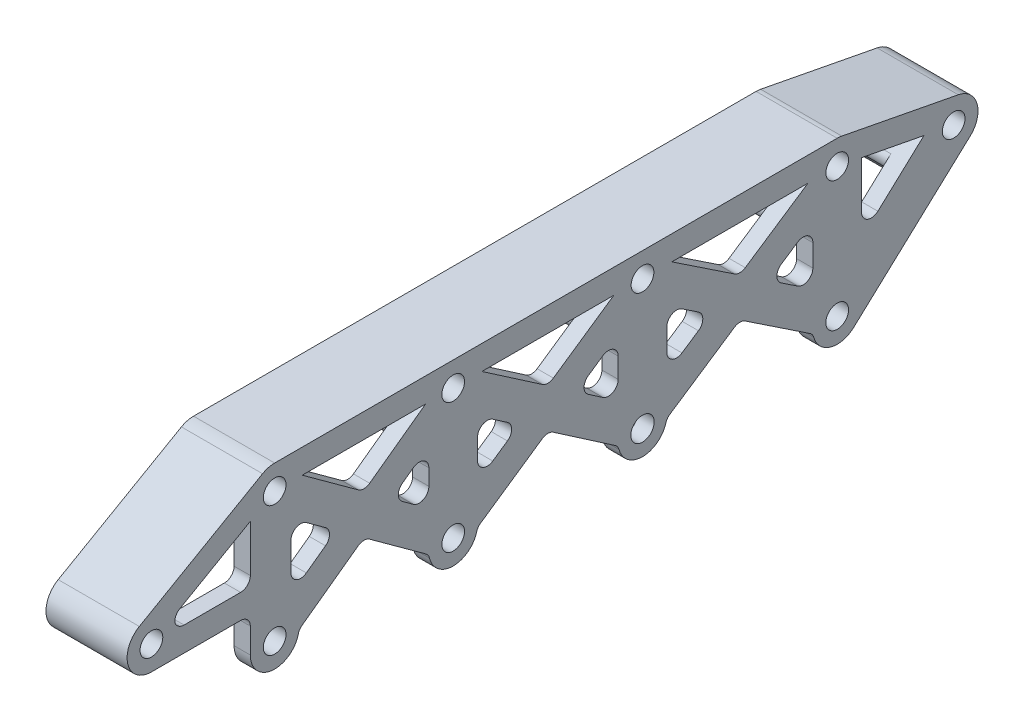
SolidWorks part; units mm, degrees
ref_plane "Front Plane" through (0, 0, 0) normal (0, 0, 1) x (1, 0, 0)
ref_plane "Top Plane" through (0, 0, 0) normal (0, 1, 0) x (1, 0, 0)
ref_plane "Right Plane" through (0, 0, 0) normal (1, 0, 0) x (0, 0, -1)
sketch "Sketch1" plane through (0, 0, 0) normal (1, 0, 0) x (0, 0, -1)
  line L0 (0, 0) -> (0, 25.4)
  line L1 (0, 25.4) -> (38.1, 25.4)
  line L2 (38.1, 25.4) -> (38.1, 0)
  line L3 (0, 25.4) -> (-37.0443, 25.4)
  line L4 (-37.0443, 25.4) -> (-71.9773, 25.4)
  line L5 (-71.9773, 25.4) -> (-71.9773, 0)
  line L6 (-37.0443, 25.4) -> (-37.0443, 0)
  line L7 (38.1, 25.4) -> (60.8901, 25.4)
  line L8 (60.8901, 25.4) -> (60.8901, 21.0111)
  line L9 (-71.9773, 25.4) -> (-71.9773, 11.5732)
  line L10 (-71.9773, 11.5732) -> (-96.0904, 11.5732)
  line L11 (-96.0904, 11.5732) -> (-71.9773, 25.4)
  line L12 (60.8901, 21.0111) -> (38.1, 25.4)
  line L13 (38.1, 0) -> (60.8901, 21.0111)
  line L14 (-67.2148, 33.6208) -> (-67.2148, 6.8107)
  line L15 (-67.2148, 6.8107) -> (-113.97, 6.8107)
  line L16 (-113.97, 6.8107) -> (-67.2148, 33.6208)
  line L17 (61.7907, 25.6877) -> (39.0006, 30.0766)
  line L18 (33.3375, 25.4) -> (33.3375, -10.8684)
  line L19 (33.3375, -10.8684) -> (64.1182, 17.5096)
  line L20 (0, 30.1625) -> (-37.0443, 30.1625)
  line L21 (0, 20.6375) -> (38.1, 20.6375)
  line L22 (-37.0443, 30.1625) -> (-71.9773, 30.1625)
  line L23 (-76.7398, 25.4) -> (-76.7398, 0)
  line L24 (-41.8068, 25.4) -> (-41.8068, 0)
  line L25 (4.7625, 0) -> (4.7625, 25.4)
  line L26 (-76.7398, 17.1792) -> (-76.7398, 16.3357)
  line L27 (-76.7398, 16.3357) -> (-78.2108, 16.3357)
  line L28 (-78.2108, 16.3357) -> (-76.7398, 17.1792)
  line L29 (59.9895, 16.3346) -> (37.1994, 20.7234)
  line L30 (42.8625, 25.4) -> (42.8625, 10.8684)
  line L31 (42.8625, 10.8684) -> (57.6619, 24.5126)
  line L32 (0, 20.6375) -> (-37.0443, 20.6375)
  line L33 (0, 30.1625) -> (38.1, 30.1625)
  line L34 (-37.0443, 20.6375) -> (-71.9773, 20.6375)
  line L35 (-67.2148, 25.4) -> (-67.2148, 0)
  line L36 (-32.2818, 25.4) -> (-32.2818, 0)
  line L37 (-4.7625, 0) -> (-4.7625, 25.4)
  line L38 (-71.9773, 0) -> (-37.0443, 25.4)
  line L39 (-37.0443, 0) -> (-71.9773, 25.4)
  line L40 (-37.0443, 0) -> (0, 25.4)
  line L41 (0, 0) -> (-37.0443, 25.4)
  line L42 (0, 0) -> (38.1, 25.4)
  line L43 (38.1, 0) -> (0, 25.4)
  line L44 (39.8612, 2.6418) -> (1.7612, 28.0418)
  line L45 (1.7612, -2.6418) -> (39.8612, 22.7582)
  line L46 (1.7955, 2.6186) -> (-35.2489, 28.0186)
  line L47 (-35.2489, -2.6186) -> (1.7955, 22.7814)
  line L48 (-75.1523, 25.4) -> (-75.1523, -6.2341)
  line L49 (-75.1523, -6.2341) -> (-35.1772, 22.8321)
  line L50 (-35.1772, 2.5679) -> (-70.1102, 27.9679)
  line L51 (36.3388, -2.6418) -> (-1.7612, 22.7582)
  line L52 (-1.7612, 2.6418) -> (36.3388, 28.0418)
  line L53 (-1.7955, -2.6186) -> (-38.8398, 22.7814)
  line L54 (-38.8398, 2.6186) -> (-1.7955, 28.0186)
  line L55 (-68.8023, 25.4) -> (-68.8023, 6.2341)
  line L56 (-68.8023, 6.2341) -> (-38.9115, 27.9679)
  line L57 (-38.9115, -2.5679) -> (-73.8445, 22.8321)
  circle A0 centre (0, 0) radius 2.286
  circle A1 centre (38.1, 0) radius 2.2225
  circle A2 centre (-71.9773, 0) radius 2.2225
  circle A3 centre (-37.0443, 0) radius 2.2225
  circle A4 centre (-71.9773, 25.4) radius 2.2225
  circle A5 centre (-37.0443, 25.4) radius 2.2225
  circle A6 centre (0, 25.4) radius 2.2225
  circle A7 centre (38.1, 25.4) radius 2.2225
  circle A8 centre (60.8901, 21.0111) radius 2.2225
  circle A9 centre (-96.0904, 11.5732) radius 2.2225
  circle A10 centre (-71.9773, 0) radius 4.7625
  circle A11 centre (-37.0443, 0) radius 4.7625
  circle A12 centre (0, 0) radius 4.7625
  circle A13 centre (38.1, 0) radius 4.7625
  circle A14 centre (38.1, 25.4) radius 4.7625
  circle A15 centre (0, 25.4) radius 4.7625
  circle A16 centre (-37.0443, 25.4) radius 4.7625
  circle A17 centre (-71.9773, 25.4) radius 4.7625
  circle A18 centre (-96.0904, 11.5732) radius 4.7625
  circle A19 centre (60.8901, 21.0111) radius 4.7625
  dimension "D2" = 4.572
  dimension "D7" = 4.445
  dimension "D8" = 4.445
  dimension "D9" = 4.445
  dimension "D10" = 4.445
  dimension "D11" = 4.445
  dimension "D12" = 4.445
  dimension "D13" = 4.445
  dimension "D16" = 4.445
  dimension "D19" = 4.445
  dimension "D20" = 9.525
  dimension "D21" = 9.525
  dimension "D22" = 9.525
  dimension "D23" = 9.525
  dimension "D24" = 9.525
  dimension "D25" = 9.525
  dimension "D26" = 9.525
  dimension "D27" = 9.525
  dimension "D28" = 9.525
  dimension "D29" = 9.525
  dimension "D1" = 25.4
  dimension "D3" = 38.1
  dimension "D4" = 25.4
  dimension "D5" = 25.4
  dimension "D6" = 25.4
  dimension "D14" = 22.7901
  dimension "D15" = 4.3889
  dimension "D17" = 13.8268
  dimension "D18" = 24.113
  dimension "D30" = 4.7625
  dimension "D31" = 4.7625
  dimension "D32" = 3.175
  dimension "D33" = 3.175
extrude "Boss-Extrude1" add sketch "Sketch1" along normal blind 15.875 contours L5 A10 L48 L49 L38 A2 | L11 A18 L10 A9 | A18 L11 L23 A17 L16 | L4 A17 L11 A4 | A16 L22 L14 L50 L4 L56 | A18 L15 L23 L10 | L10 A18 L11 A9 | A17 L11 L23 L10 L48 | A17 L48 L10 L9 | L48 A17 L9 A4 L11 | L11 A17 L48 | A17 L23 L11 | L57 A17 L55 L39 A4 L9 | A4 L39 L55 L4 | A17 L50 L14 L22 | L4 L50 L14 | L39 A17 L4 L55 | L38 L57 L56 L35 | A10 L49 L57 L38 L35 | A10 L38 L35 L15 L56 L55 L5 | L38 A10 L5 A2 | L49 A10 | A10 L35 L38 | L48 A10 | A10 L48 L15 L23 | L48 L10 L23 L15 | L10 L48 L15 L5 | A10 L5 L15 L48 | L55 L57 L34 L9 L5 L15 | L55 A17 L39 | L9 A17 L57 | A17 L57 L34 L55 | A17 L34 L57 | L57 L55 L34 | L56 L15 L35 | A17 L14 L50 | L39 L56 L50 L34 | L57 L56 L39 L34 L14 | L34 L50 L4 L14 L39 | A17 L39 L14 | L34 L39 L35 | A17 L55 L34 L35 L39 | L57 L14 L34 L55 | L57 L38 L39 L56 | L56 L39 L38 L50 | L49 L50 L38 L39 | L57 L49 L39 L38 | L56 L50 L38 L34 | L50 L49 L24 L34 L38 | L24 L50 L49 L39 | A16 L46 L3 L54 A15 L20 | L3 A16 L4 A5 | L32 L46 L3 L36 L41 | A11 L6 L34 L49 L24 L50 | A11 L54 L36 L53 L32 L6 | A11 L24 L39 L49 L57 | A11 L50 L24 L39 | L50 A11 L39 A3 L6 | A11 L40 A3 L39 | A11 L39 L24 | L40 A11 L54 L6 A3 | A11 L40 L36 L54 | L54 L36 L40 L53 | A11 L47 L53 L40 L36 | L41 L54 L46 L32 | L53 L54 L41 L32 L36 | L56 L34 L38 L24 L4 | L4 A16 L38 A5 | A16 L56 L4 | A16 L24 L38 | A16 L38 L24 L34 L49 | L38 L34 L24 | L24 L49 L34 | L38 A16 L49 L6 A5 | A16 L3 L46 | L41 A16 L3 A5 | A16 L53 L32 L36 L41 | L32 L41 L36 | L53 L36 L32 | L53 A16 L41 A5 L6 | A16 L41 L36 | L6 A16 L53 L49 | L49 A16 L6 | A16 L49 L34 | A16 L32 L53 | L49 L53 L6 | L54 A11 L6 L50 | L6 A11 L50 | A11 L36 L40 | L6 L54 L50 | L54 L53 L40 L41 | L54 L41 L40 L46 | L53 L47 L41 L40 | L41 L47 L46 L40 | L46 L47 L37 L32 L40 | L54 L46 L40 L32 | L47 L41 L37 L46 | A12 L37 L41 L47 L53 | L54 L32 L40 L37 L3 | L40 L32 L37 | L1 A15 L3 A6 | A15 L54 L3 | L3 A15 L40 A6 | A15 L37 L40 | A15 L40 L37 L32 L47 | L37 L47 L32 | L40 A15 L47 L0 A6 | L47 A15 L0 | A15 L47 L32 | L51 A15 L43 A6 L0 | L0 A15 L51 L47 | A15 L21 L51 | A15 L51 L21 L25 L43 | L51 L25 L21 | A15 L44 L1 L52 A14 L33 | L43 A15 L1 A6 | A15 L1 L44 | A15 L43 L25 | L21 L44 L1 L25 L43 | L21 L43 L25 | L47 L51 L0 | A12 L46 L37 L41 | L46 A12 L41 A0 L0 | A12 L42 A0 L41 | A12 L41 L37 | L42 A12 L52 L0 A0 | L0 A12 L46 | L52 A12 L0 L46 | A12 L42 L25 L52 | A12 L25 L42 | L52 L25 L42 L51 | A12 L45 L51 L42 L25 | A12 L0 L32 L47 L37 L46 | A12 L52 L25 L51 L21 L0 | L51 L52 L43 L21 L25 | L43 L52 L44 L21 | L52 L43 L42 L44 | L52 L51 L42 L43 | L51 L45 L43 L42 | L43 L45 L44 L42 | L0 L52 L46 | L52 L21 L42 L18 L1 | L7 A14 L1 A7 | A19 L17 A14 L7 | A14 L52 L1 | L1 A14 L42 A7 | L52 L44 L42 L21 | L44 L45 L18 L21 L42 | L7 A19 L12 A8 L8 | A19 L7 L8 A8 L13 | A19 L29 L13 A13 L19 | L43 A13 L13 A1 | L51 L18 L43 L45 | L45 L43 L18 L44 | A13 L2 L29 L21 L45 L18 L44 | A13 L13 L29 L31 L30 L2 | A19 L12 L31 L29 L13 | A19 L13 L29 | L12 A19 L13 A8 | A19 L31 L12 | L2 A14 L12 A7 | A14 L2 L29 L30 L12 | L42 A14 L45 L2 A7 | L42 L21 L18 | A14 L18 L42 | A14 L42 L18 L21 L45 | L18 L45 L21 | L45 A14 L2 | A14 L45 L21 L29 | L29 L2 L21 | A14 L29 L21 | L12 A14 L7 A7 | A14 L12 L30 | A13 L18 L51 | A13 L43 L18 | A13 L44 L18 L43 | L44 A13 L43 A1 L2 | L2 A13 L44 | L13 A13 L2 A1 | A19 L7 L30 L12 L31 region at (0, 3.0311, 1.7302) region at (0, 3.0092, -1.756) region at (0, -2.2991, 0.7125) region at (0, 3.8327, -0.0083) region at (0, 2.2442, 4.5084) region at (0, 4.8141, 3.582) region at (0, 4.7476, -3.6056) region at (0, 2.1905, -4.5191) region at (0, 4.4269, 0.3865) region at (0, 4.4125, -0.4081) region at (0, 8.3932, 9.5713) region at (0, 5.5211, 10.9661) region at (0, 12.6923, 2.2321) region at (0, 5.4983, -11.216) region at (0, 8.3462, -9.794) region at (0, 12.691, -2.2413) region at (0, 10.7752, 18.5222) region at (0, 12.7, 15.7149) region at (0, 12.7, -16.1881) region at (0, 10.7921, -19.05) region at (0, 20.9731, 0.3865) region at (0, 20.684, -0.9787) region at (0, 20.6793, 0.9231) region at (0, 20.9875, -0.4081) region at (0, 16.8146, 9.7612) region at (0, 19.8533, 3.6188) region at (0, 14.6248, 18.5222) region at (0, 12.7, 21.3294) region at (0, 5.5211, 26.0782) region at (0, 19.8947, -3.6483) region at (0, 16.8393, -10.0149) region at (0, 14.6079, -19.05) region at (0, 12.7, -21.9119) region at (0, 5.4995, -26.8827) region at (0, 22.3881, 1.7178) region at (0, 21.5673, -0.0083) region at (0, 21.3763, -3.5648) region at (0, 21.3553, 3.5433) region at (0, 22.4099, -1.7433) region at (0, 21.1365, 5.4903) region at (0, 18.0818, 13.3021) region at (0, 8.3932, 27.473) region at (0, 16.8146, 27.2832) region at (0, 18.0818, 23.7423) region at (0, -4.6404, 37.1085) region at (0, 21.1667, -5.5562) region at (0, 18.0698, -13.6779) region at (0, 18.0698, -24.4221) region at (0, 16.8393, -28.0851) region at (0, 8.3462, -28.306) region at (0, -0.4926, -33.3517) region at (0, 24.3368, 3.4308) region at (0, 23.1558, 4.5084) region at (0, 23.2095, -4.5191) region at (0, 24.3585, -3.4399) region at (0, 22.4886, 7.5534) region at (0, 4.8141, 33.4624) region at (0, 2.2442, 32.5359) region at (0, 22.4886, 29.4909) region at (0, 21.1365, 31.5541)
sketch "Sketch2" plane through (0, 0, 0) normal (-1, 0, 0) x (0, 0, 1)
  line L12 (-38.1, 0) -> (-38.1, 19.05)
  line L13 (-38.1, 19.05) -> (71.9773, 19.924)
  line L14 (71.9773, 19.924) -> (71.9773, 0)
  line L15 (71.9773, 0) -> (-38.1, 0)
  line L16 (71.9773, 4.7625) -> (-38.1, 4.7625)
  line L17 (71.9773, -4.7625) -> (-38.1, -4.7625)
  line L18 (91.3067, 11.5732) -> (76.7398, 11.5732)
  line L19 (76.7398, 11.5732) -> (76.7398, 6.8107)
  line L20 (96.0904, 6.8107) -> (76.7398, 6.8107)
  line L24 (76.7398, 0) -> (76.7398, 6.8107)
  line L25 (76.7398, 6.8107) -> (96.0904, 6.8107)
  line L26 (98.4594, 15.7047) -> (74.3464, 29.5315)
  line L27 (71.9773, 30.1625) -> (-38.1, 30.1625)
  line L28 (-39.0006, 30.0766) -> (-61.7907, 25.6877)
  line L29 (-64.1182, 17.5096) -> (-41.3282, -3.5015)
  line L30 (-33.3852, -0.6727) -> (-19.05, 8.8841)
  line L31 (-19.05, 8.8841) -> (-4.7148, -0.6727)
  line L32 (4.7231, -0.6112) -> (18.5222, 8.8503)
  line L33 (18.5222, 8.8503) -> (32.3212, -0.6112)
  line L34 (41.7825, -0.4804) -> (54.5108, 8.7744)
  line L35 (54.5108, 8.7744) -> (67.2391, -0.4804)
  line L36 (76.7398, 0) -> (76.7398, 6.8107)
  line L37 (76.7398, 6.8107) -> (96.0904, 6.8107)
  line L38 (98.4594, 15.7047) -> (74.3464, 29.5315)
  line L39 (71.9773, 30.1625) -> (-38.1, 30.1625)
  line L40 (-39.0006, 30.0766) -> (-61.7907, 25.6877)
  line L41 (-64.1182, 17.5096) -> (-41.3282, -3.5015)
  line L42 (-33.3852, -0.6727) -> (-19.05, 8.8841)
  line L43 (-19.05, 8.8841) -> (-4.7148, -0.6727)
  line L44 (4.7231, -0.6112) -> (18.5222, 8.8503)
  line L45 (18.5222, 8.8503) -> (32.3212, -0.6112)
  line L46 (41.7825, -0.4804) -> (54.5108, 8.7744)
  line L47 (54.5108, 8.7744) -> (67.2391, -0.4804)
  circle A9 centre (-38.1, 0) radius 21.2725
  circle A10 centre (71.9773, 0) radius 21.2725
  circle A11 centre (0, 0) radius 21.2725
  circle A12 centre (37.0443, 0) radius 21.2725
  circle A13 centre (96.0904, 11.5732) radius 4.7837
  arc A16 (67.2391, -0.4804) -> (76.7398, 0) centre (71.9773, 0) ccw
  arc A17 (96.0904, 6.8107) -> (98.4594, 15.7047) centre (96.0904, 11.5732) ccw
  arc A18 (74.3464, 29.5315) -> (71.9773, 30.1625) centre (71.9773, 25.4) ccw
  arc A19 (-38.1, 30.1625) -> (-39.0006, 30.0766) centre (-38.1, 25.4) ccw
  arc A20 (-61.7907, 25.6877) -> (-64.1182, 17.5096) centre (-60.8901, 21.0111) ccw
  arc A21 (-41.3282, -3.5015) -> (-33.3852, -0.6727) centre (-38.1, 0) ccw
  arc A22 (-4.7148, -0.6727) -> (4.7231, -0.6112) centre (0, 0) ccw
  arc A23 (32.3212, -0.6112) -> (41.7825, -0.4804) centre (37.0443, 0) ccw
  arc A24 (67.2391, -0.4804) -> (76.7398, 0) centre (71.9773, 0) ccw
  arc A25 (96.0904, 6.8107) -> (98.4594, 15.7047) centre (96.0904, 11.5732) ccw
  arc A26 (74.3464, 29.5315) -> (71.9773, 30.1625) centre (71.9773, 25.4) ccw
  arc A27 (-38.1, 30.1625) -> (-39.0006, 30.0766) centre (-38.1, 25.4) ccw
  arc A28 (-61.7907, 25.6877) -> (-64.1182, 17.5096) centre (-60.8901, 21.0111) ccw
  arc A29 (-41.3282, -3.5015) -> (-33.3852, -0.6727) centre (-38.1, 0) ccw
  arc A30 (-4.7148, -0.6727) -> (4.7231, -0.6112) centre (0, 0) ccw
  arc A31 (32.3212, -0.6112) -> (41.7825, -0.4804) centre (37.0443, 0) ccw
  dimension "D2" = 19.05
  dimension "D3" = 4.7625
  dimension "D5" = 42.545
  dimension "D6" = 42.545
  dimension "D7" = 42.545
  dimension "D8" = 42.545
  dimension "D1" = 0
  dimension "D4" = 4.7625
extrude "Cut-Extrude1" cut sketch "Sketch2" against normal blind 12.7 contours A29 L41 A9 A11 L17 | L41 A29 L42 L15 L12 L13 A9 | A11 A9 L13 L12 L16 L42 | L15 L42 L16 L12 | A29 L17 A11 L15 L42 | A12 L17 A9 A11 | A11 A12 A10 L17 | A24 L17 A12 A10 L37 L36 | L47 A24 L36 L19 L18 A10 L13 L14 L15 | L37 A10 L18 L19 | A13 L18 A10 L37 | A12 L47 L16 L14 L13 A10 | A12 A10 L13 | L16 L47 L15 L14 | A12 L15 L47 L16 | L15 A12 L16 A10 | A10 A12 L13 A11 L45 L16 L46 | L47 A12 A10 L46 | A24 L47 L15 A12 L17 | L17 A12 L15 A10 | A10 A12 L17 | A31 L17 A10 L15 L46 | A10 L16 L46 L15 | L16 A12 L47 L46 A10 | A12 L16 L47 | A10 L46 L16 | A11 L13 A9 | A12 A11 L13 A9 L43 L16 L44 | A12 L13 A11 | L13 A11 | L13 A12 | L16 A11 L15 A9 | A11 L16 L42 L15 | L42 A11 L16 A9 L43 | A11 L42 L16 | A9 L16 L43 | A9 L15 L43 L16 | L17 A11 A9 | L15 A11 L17 A9 | A30 L43 L15 A9 L17 | A30 L17 A12 L15 L44 | A12 L16 L44 L15 | A31 L45 L15 A11 L17 | A11 L15 L45 L16 | A9 A11 L42 L43 | L15 L44 L16 L43 | L44 A12 L16 A11 L45 | A12 L44 L16 | A11 L16 L45 | L16 A12 L15 A11 | L15 A12 L17 A11 | L17 A12 A11 | A11 A12 L44 L45 | L15 L46 L16 L45 | L43 A30 L44 L15 | L45 A31 L46 L15 region at (0, 9.5127, -43.8898) region at (0, 2.6862, -33.2234) region at (0, 11.5571, -30.0819) region at (0, 2.0413, -25.223) region at (0, -2.5104, -27.7415) region at (0, 6.0273, -21.857) region at (0, 2.2766, -19.05) region at (0, -2.2766, -19.05) region at (0, 16.3314, -18.9813) region at (0, 6.3483, -19.05) region at (0, 8.9912, -19.05) region at (0, 2.0413, -12.877) region at (0, -2.5104, -10.3585) region at (0, -8.7603, -41.8121) region at (0, -6.4192, -19.05) region at (0, 20.1226, -0.1598) region at (0, 11.6634, -0.1095) region at (0, 6.0273, -16.243) region at (0, 2.6854, -0.1105) region at (0, -1.9926, -0.0089) region at (0, -11.8911, -0.1998) region at (0, 16.8192, 18.5975) region at (0, 2.0108, 12.2282) region at (0, -2.5192, 9.8216) region at (0, -6.7851, 18.5222) region at (0, -12.0578, 36.5584) region at (0, 20.2982, 36.8832) region at (0, 11.8436, 36.6748) region at (0, 9.1309, 18.5222) region at (0, 5.8431, 15.3711) region at (0, 2.2981, 18.5222) region at (0, -2.2981, 18.5222) region at (0, -2.5192, 27.2228) region at (0, -8.2522, 76.3208) region at (0, -7.4129, 54.5108) region at (0, 17.4909, 54.5919) region at (0, 6.399, 18.5222) region at (0, 5.8431, 21.6733) region at (0, 2.0108, 24.8162) region at (0, -2.5432, 45.7915) region at (0, -2.0005, 37.0293) region at (0, -2.3223, 54.5108) region at (0, -2.5432, 63.2301) region at (0, 10.3935, 76.3396) region at (0, 11.9857, 64.599) region at (0, 9.2899, 54.5108) region at (0, 2.6828, 36.825) region at (0, 2.3223, 54.5108) region at (0, 1.9194, 47.9575) region at (0, 8.8496, 91.976) region at (0, 9.1286, 83.9355) region at (0, 1.9194, 61.0642) region at (0, 5.444, 50.6749) region at (0, 6.2702, 54.5108) region at (0, 5.444, 58.3467) region at (0, 2.6809, 67.4343)
fillet "Fillet1" radius 1.905 10 edges at (6.35, 20.7325, 76.7398) (6.35, 19.7512, 50.2121) (6.35, 19.8202, 58.9045) (6.35, 19.5341, 22.8748) (6.35, 19.4658, 14.2691) (6.35, 19.1697, -23.0307) (6.35, 19.2336, -14.9734) (6.35, 20.7325, -42.8625) (6.35, 10.5516, -56.5711) (6.35, 17.5546, -50.1148)
fillet "Fillet2" radius 1.905 35 edges at (14.2875, 10.8684, -42.8625) (14.2875, 16.5159, -19.05) (7.9375, 13.9423, 91.9589) (7.9375, 11.5732, 91.3279) (14.2875, 11.5732, 76.7398) (14.2875, 16.6256, 54.5108) (14.2875, 12.7, 59.9097) (14.2875, 6.2341, 68.8023) (14.2875, 19.1659, 68.8023) (14.2875, 12.7, 49.1119) (14.2875, 7.3884, 41.8068) (14.2875, 18.0116, 41.8068) (14.2875, 12.7, 24.1367) (14.2875, 18.2849, 32.2818) (14.2875, 7.1151, 32.2818) (14.2875, 16.5497, 18.5222) (14.2875, 12.7, 12.9077) (14.2875, 7.1151, 4.7625) (14.2875, 18.2849, 4.7625) (14.2875, 12.7, -13.3262) (14.2875, 6.9909, -4.7625) (14.2875, 18.4091, -4.7625) (14.2875, 12.7, -24.7738) (14.2875, 6.9909, -33.3375) (14.2875, 18.4091, -33.3375) (14.2875, 6.8107, 76.7398) (14.2875, -0.4804, 67.2391) (14.2875, 8.7744, 54.5108) (14.2875, -0.6112, 32.3212) (14.2875, 8.8503, 18.5222) (14.2875, -0.4804, 41.7825) (14.2875, -0.6112, 4.7231) (14.2875, -0.6727, -4.7148) (14.2875, 8.8841, -19.05) (14.2875, -0.6727, -33.3852)
